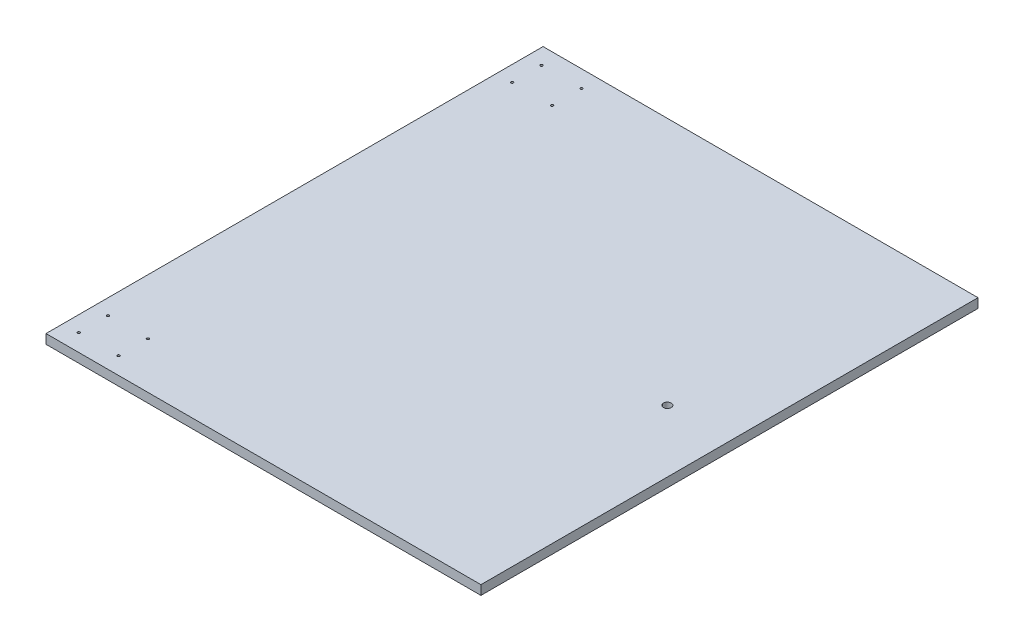
SolidWorks part; units mm, degrees
material "Cedar"
ref_plane "Front" through (0, 0, 0) normal (0, 0, 1) x (1, 0, 0)
ref_plane "Top" through (0, 0, 0) normal (0, 1, 0) x (1, 0, 0)
ref_plane "Right" through (0, 0, 0) normal (1, 0, 0) x (0, 0, -1)
sketch "Sketch1" plane through (0, 0, 0) normal (0, 1, 0) x (1, 0, 0)
  line L1 (-266.7, -304.8) -> (266.7, -304.8)
  line L2 (-266.7, -304.8) -> (-266.7, 304.8)
  line L3 (-266.7, 304.8) -> (266.7, 304.8)
  line L4 (266.7, -304.8) -> (266.7, 304.8)
  line L5 (-266.7, -304.8) -> (266.7, 304.8) construction
  line L6 (-266.7, 304.8) -> (266.7, -304.8) construction
  point P0 (0, 0)
  dimension "D1" = 609.6
  dimension "D2" = 533.4
extrude "Boss-Extrude1" add sketch "Sketch1" along normal blind 11.4554 contours L1 L4 L3 L2
sketch "Sketch3" plane through (0, 11.4554, 0) normal (0, 1, 0) x (1, 0, 0)
  line L0 (266.7, -304.8) -> (266.7, 304.8) construction
  line L1 (-247.65, 283.8) -> (-247.65, 247.8) construction
  line L2 (-247.65, 247.8) -> (-198.65, 247.8) construction
  line L3 (-198.65, 247.8) -> (-198.65, 283.8) construction
  line L4 (-198.65, 283.8) -> (-247.65, 283.8) construction
  line L5 (-266.7, 304.8) -> (266.7, 304.8) construction
  line L6 (-266.7, -304.8) -> (-266.7, 304.8) construction
  line L7 (130.8452, 0) -> (-366.2568, 0) construction
  circle A0 centre (190.5, 0) radius 4.826
  circle A1 centre (-198.65, 283.8) radius 1.5
  circle A2 centre (-247.65, 283.8) radius 1.5
  circle A3 centre (-247.65, 247.8) radius 1.5
  circle A4 centre (-198.65, 247.8) radius 1.5
  circle A5 centre (-198.65, -247.8) radius 1.5
  circle A6 centre (-247.65, -247.8) radius 1.5
  circle A7 centre (-247.65, -283.8) radius 1.5
  circle A8 centre (-198.65, -283.8) radius 1.5
  dimension "D1" = 9.652
  dimension "D2" = 76.2
  dimension "D3" = 3
  dimension "D4" = 36
  dimension "D5" = 49
  dimension "D6" = 21
  dimension "D7" = 19.05
extrude "Cut-Extrude1" cut sketch "Sketch3" against normal through all
